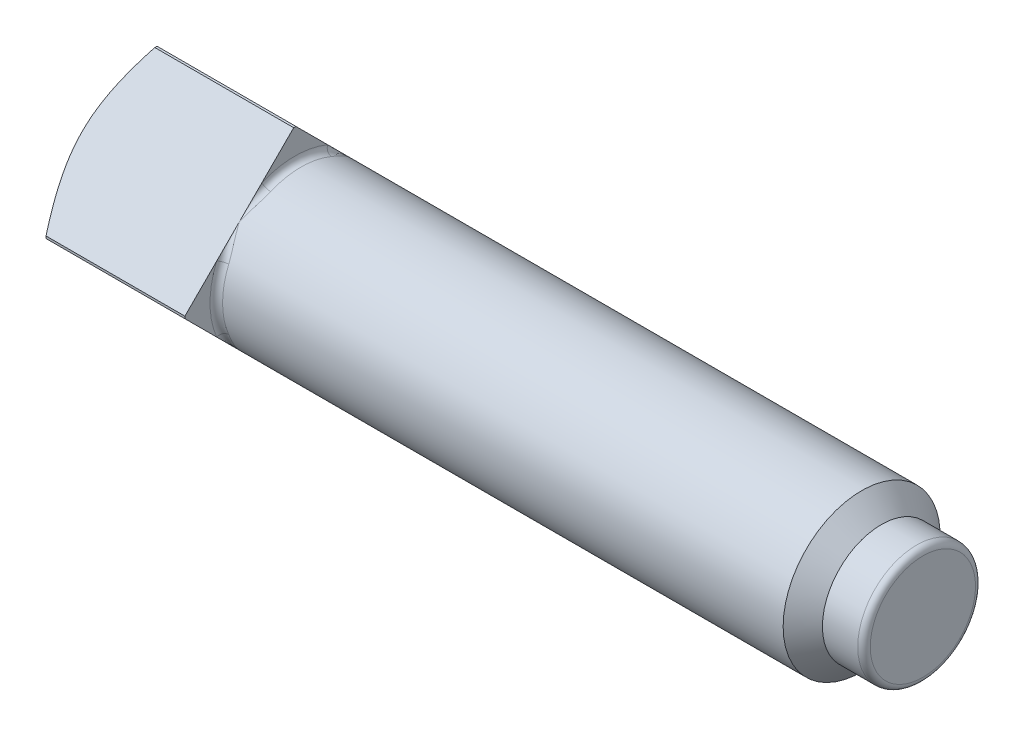
SolidWorks part; units mm, degrees
extrude "BaseHead" add sketch "SquareSke" along normal blind 20
sketch "SquareSke" plane through (0, 0, 0) normal (1, 0, 0) x (0, 0, -1)
  line L0 (13.9993, -0.1429) -> (0.1429, -13.9993)
  line L1 (-0.1429, -13.9993) -> (-13.9993, -0.1429)
  line L2 (-14, 0) -> (14, 0) construction
  line L3 (-13.9993, -0.1429) -> (13.9993, -0.1429) construction
  line L4 (13.9993, 0.1429) -> (0.1429, 13.9993)
  line L5 (-0.1429, 13.9993) -> (-13.9993, 0.1429)
  arc A0 (-13.9993, 0.1429) -> (-13.9993, -0.1429) centre (0, 0) ccw
  arc A1 (-0.1429, -13.9993) -> (0.1429, -13.9993) centre (0, 0) ccw
  arc A2 (13.9993, -0.1429) -> (13.9993, 0.1429) centre (0, 0) ccw
  arc A3 (0.1429, 13.9993) -> (-0.1429, 13.9993) centre (0, 0) ccw
  dimension "Dflats" = 28
  dimension "Width_flats" = 20
ref_plane "Plane1" through (0, 0, 0) normal (0, 0, 1) x (1, 0, 0)
ref_plane "Plane2" through (0, 0, 0) normal (0, 1, 0) x (1, 0, 0)
ref_plane "Plane3" through (0, 0, 0) normal (1, 0, 0) x (0, 0, -1)
sketch "BodySke" plane through (0, 0, 0) normal (0, 0, 1) x (1, 0, 0)
  line L0 (130.7115, 16) -> (81.0004, 16) construction
  line L1 (0, 0) -> (100, 0)
  line L2 (0, 10) -> (0, 0)
  line L3 (0, 10) -> (94.7, 10)
  line L4 (100, 0) -> (100, 7.5)
  line L5 (20, 13.9993) -> (20, 0.1429) construction
  line L6 (94.7, 7.5) -> (94.7, 10)
  line L7 (0, 0) -> (120.6874, 0) construction
  line L10 (22.5, 15.24) -> (22.5, -1.27) construction
  line L11 (100, 7.5) -> (94.7, 7.5)
  line L13 (20, 13.9993) -> (20, 0.1429) construction
  dimension "Advance" = 2.5
  dimension "Dog_dia" = 15
  dimension "Diameter" = 20
revolve "BaseBody" add sketch "BodySke" angle 360 about L7
cosmetic thread "ThreadCosmetic" [suppressed] parameters "Thread_length"=72.2, "Thread_minor"=16
sketch "HeadChamSke" plane through (0, 0, 0) normal (0, 0, 1) x (1, 0, 0)
  line L0 (0, 10) -> (5.2782, 19.1421)
  line L1 (0, 13.9993) -> (0, 0.1429) construction
  line L2 (5.2782, 19.1421) -> (5.2782, 24.1421)
  line L3 (5.2782, 24.1421) -> (-10, 24.1421)
  line L4 (-10, 24.1421) -> (-10, 10)
  line L5 (-10, 10) -> (0, 10)
  line L6 (0, 0) -> (99.06, 0) construction
  line L7 (20, 14.1421) -> (0, 14.1421) construction
  dimension "D1" = 10
  dimension "D2" = 5
  dimension "D3" = 10
  dimension "D4" = 5
  dimension "Head_ch_ang" = 30
revolve "HeadChamfer" cut sketch "HeadChamSke" angle 360 about L6
fillet "HeadFillet" radius 0.8 4 edges at (20, 0, -10) (20, 10, 0) (20, 0, 10) (20, -10, 0)
fillet "BaseBodyFillet" radius 0.8 1 edges at (100, 0, 7.5)
chamfer "PointChamfer" distance 2.5 angle 45 1 edges at (94.7, 0, 10)
sketch "ThdSchSke" plane through (0, 0, 0) normal (0, 0, 1) x (1, 0, 0)
  line L0 (22.8, -8) -> (21.3996, -10)
  line L1 (22.8, -8) -> (24.2004, -10)
  line L2 (24.2004, -10) -> (24.2004, -12.5)
  line L3 (-3.175, 0) -> (5.1513, 0) construction
  line L5 (24.2004, -12.5) -> (21.3996, -12.5)
  line L6 (21.3996, -12.5) -> (21.3996, -10)
  dimension "Diameter" = 20
  dimension "Thread_minor" = 16
  dimension "Start" = 22.8
revolve "ThreadSchematic" [suppressed] cut sketch "ThdSchSke" angle 360 about L3
pattern_linear "ThdSchPat" [suppressed]
equation "\"Thread_minor@ThreadCosmetic\" = \"Minor_dia@BodySke\""
equation "\"D1@HeadChamSke\" = \"Width_flats@SquareSke\" / 2"
equation "\"Fillet_Radius@BaseBodyFillet\" = \"Fillet_Radius@HeadFillet\""
equation "\"Dist@PointChamfer\" =  ( \"Diameter@BodySke\" - \"Dog_dia@BodySke\" )  / 2"
equation "\"Thread_length@ThreadCosmetic\" = \"Length@BodySke\" - \"Dog_Lg@BodySke\" - \"Advance@BodySke\""
equation "\"Thread_minor@ThdSchSke\" = \"Minor_dia@BodySke\""
equation "\"Diameter@ThdSchSke\" = \"Diameter@BodySke\""
equation "\"Overcut@ThdSchSke\" = \"Diameter@BodySke\" * 1.25"
equation "\"Start@ThdSchSke\" = \"Head_ht@BaseHead\" + \"Length@BodySke\" - 2 * \"Advance@BodySke\" - \"Thread_length@ThreadCosmetic\"  '---Non-countersunk---"
equation "\"Num_threads@ThdSchPat\" = int( \"Thread_length@ThreadCosmetic\" / \"Advance@BodySke\" + 0.999 )  + 1"
equation "\"Advance@ThdSchPat\" = \"Thread_length@ThreadCosmetic\" /  (\"Num_threads@ThdSchPat\" - 1) 'relax it"
equation "\"Num_threads@ThdSchPat\" = \"Num_threads@ThdSchPat\" - sgn( \"Num_threads@ThdSchPat\" - 1) '---chamfered tips only---"
